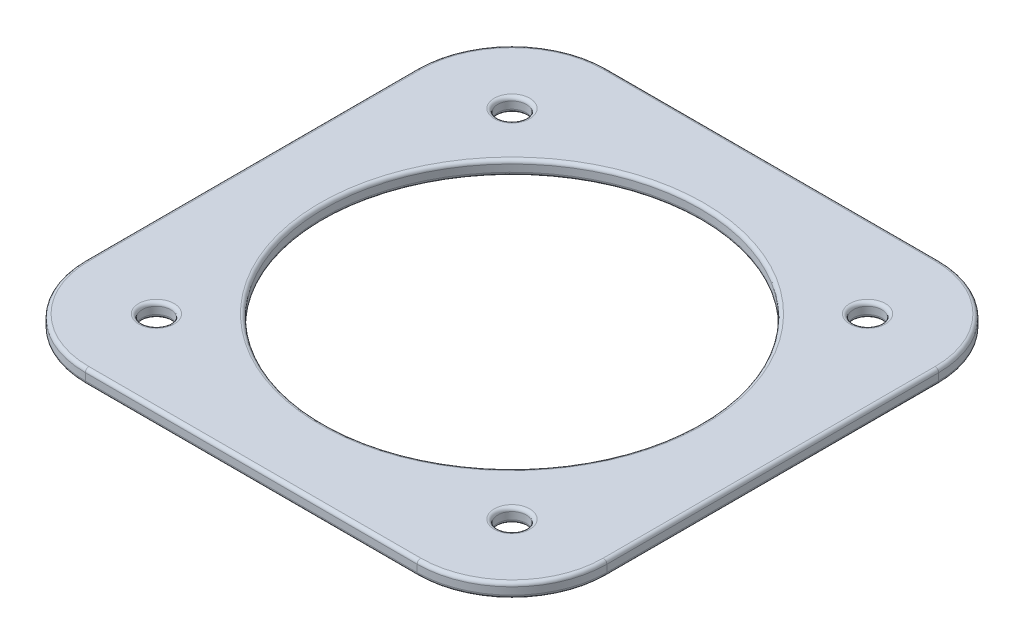
SolidWorks part; units mm, degrees
material "ABS"
ref_plane "Front Plane" through (0, 0, 0) normal (0, 0, 1) x (1, 0, 0)
ref_plane "Top Plane" through (0, 0, 0) normal (0, 1, 0) x (1, 0, 0)
ref_plane "Right Plane" through (0, 0, 0) normal (1, 0, 0) x (0, 0, -1)
sketch "Sketch1" plane through (0, 0, 0) normal (0, 1, 0) x (1, 0, 0)
  line L1 (-70, -110) -> (70, -110)
  line L2 (-110, -70) -> (-110, 70)
  line L3 (-70, 110) -> (70, 110)
  line L4 (110, -70) -> (110, 70)
  line L5 (-110, -110) -> (110, 110) construction
  line L6 (-110, 110) -> (110, -110) construction
  circle A1 centre (0, 0) radius 79.5
  arc A2 (-70, -110) -> (-110, -70) centre (-70, -70) cw
  circle A3 centre (0, 0) radius 87.5 construction
  arc A4 (70, -110) -> (110, -70) centre (70, -70) ccw
  arc A5 (70, 110) -> (110, 70) centre (70, 70) cw
  arc A6 (-110, 70) -> (-70, 110) centre (-70, 70) cw
  dimension "D1" = 220
  dimension "D2" = 8
  dimension "D3" = 40
extrude "Boss-Extrude1" add sketch "Sketch1" along normal blind 6
hole_wizard "CBORE for M10 SHCS" positions "Sketch2" profile "Sketch3" counterbore size "M10" standard "ANSI Metric" end condition through all
sketch "Sketch2" plane through (0, 21, 0) normal (0, 1, 0) x (1, 0, 0)
  line L1 (75, -75) -> (-75, -75) construction
  line L2 (75, -75) -> (75, 75) construction
  line L3 (75, 75) -> (-75, 75) construction
  line L4 (-75, -75) -> (-75, 75) construction
  line L5 (75, -75) -> (-75, 75) construction
  line L6 (75, 75) -> (-75, -75) construction
  point P36 (0, 0)
  point P198 (-75, 75)
  point P201 (75, 75)
  point P204 (75, -75)
  point P207 (-75, -75)
sketch "Sketch3" plane through (0, 21, 0) normal (1, 0, 0) x (0, 0, 1)
  line L0 (0, 0) -> (0, 21)
  line L1 (0, 21) -> (6, 21)
  line L2 (6, 21) -> (6, 10)
  line L3 (6, 10) -> (9, 10)
  line L4 (9, 10) -> (9, 0)
  line L5 (9, 0) -> (0, 0)
  line L6 (0, -6.35) -> (0, 107.95) construction
  dimension "Thru Hole Dia." = 12
  dimension "Thru Hole Depth" = 21
  dimension "C'Bore Dia." = 18
  dimension "C'Bore Depth" = 10
fillet "Fillet1" radius 1.5 26 edges at (0, 0, 79.5) (0, 0, 110) (98.2843, 0, 98.2843) (110, 0, 0) (98.2843, 0, -98.2843) (0, 0, -110) (-98.2843, 0, -98.2843) (-110, 0, 0) (-98.2843, 0, 98.2843) (0, 6, 79.5) (-110, 6, 0) (-98.2843, 6, -98.2843) (0, 6, -110) (98.2843, 6, -98.2843) (110, 6, 0) (98.2843, 6, 98.2843) (0, 6, 110) (-98.2843, 6, 98.2843) (-75, 0, 81) (75, 0, 81) (75, 0, -69) (-75, 0, -69) (-75, 6, 69) (75, 6, 69) (75, 6, -81) (-75, 6, -81)
